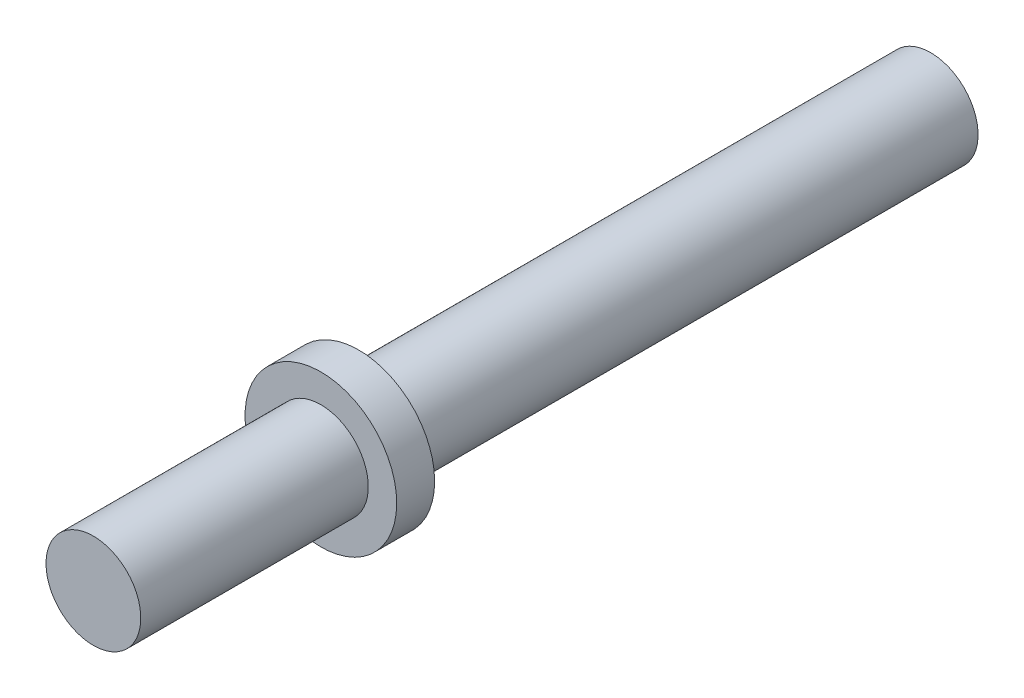
SolidWorks part; units mm, degrees
material "PVC Rigid"
ref_plane "Front Plane" through (0, 0, 0) normal (0, 0, 1) x (1, 0, 0)
ref_plane "Top Plane" through (0, 0, 0) normal (0, 1, 0) x (1, 0, 0)
ref_plane "Right Plane" through (0, 0, 0) normal (1, 0, 0) x (0, 0, -1)
sketch "Sketch1" plane through (0, 0, 0) normal (0, 0, 1) x (1, 0, 0)
  circle A0 centre (-32.0187, -34.6434) radius 1.5
extrude "Plunger_stem" add sketch "Sketch1" along normal blind 26.4999 from offset 17.5001
sketch "Sketch2" plane through (0, 0, 0) normal (0, 0, 1) x (1, 0, 0)
  circle A0 centre (-32.0187, -34.6434) radius 2.4
extrude "Captive_shoulder" add sketch "Sketch2" along normal blind 1.2 from offset 35.6
sketch "Sketch3" plane through (0, 0, 0) normal (0, 0, 1) x (1, 0, 0)
  circle A0 centre (-32.0187, -34.6434) radius 2.8
extrude "Finger_button_cap_D5p6" [suppressed] add sketch "Sketch3" along normal blind 1.2 from offset 42.8
